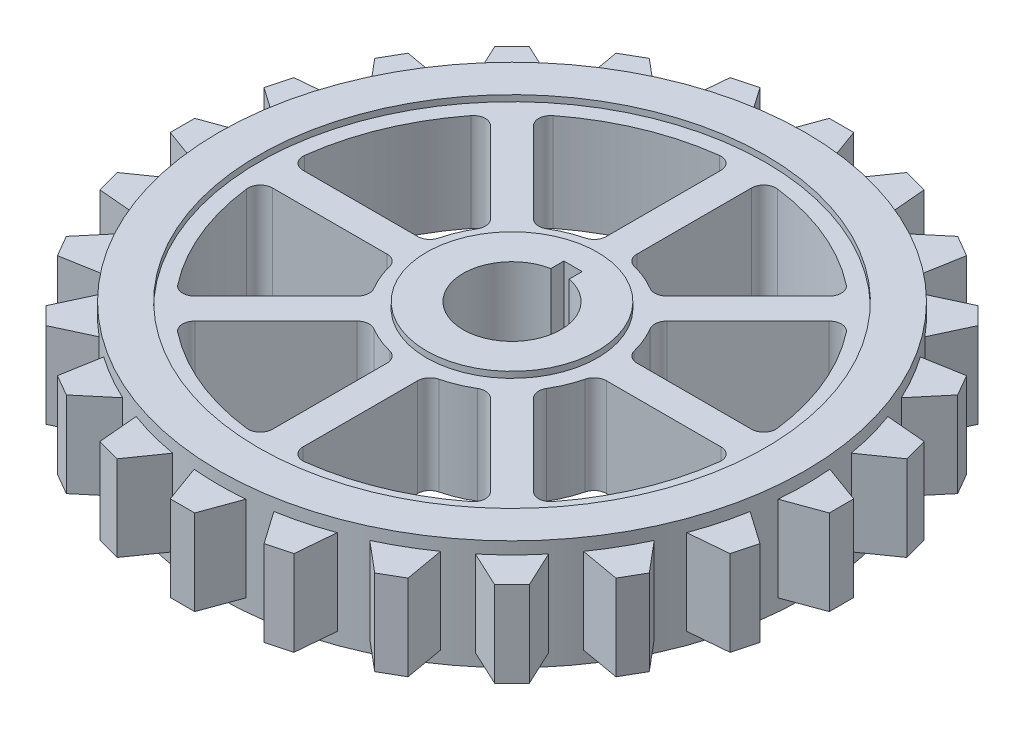
SolidWorks part; units mm, degrees
ref_plane "Front Plane" through (0, 0, 0) normal (0, 0, 1) x (1, 0, 0)
ref_plane "Top Plane" through (0, 0, 0) normal (0, 1, 0) x (1, 0, 0)
ref_plane "Right Plane" through (0, 0, 0) normal (1, 0, 0) x (0, 0, -1)
sketch "Sketch1" plane through (0, 0, 0) normal (0, 1, 0) x (1, 0, 0)
  line L0 (0, 0) -> (0, 10) construction
  line L1 (-1.5, 7.8581) -> (-1.5, 10)
  line L2 (-1.5, 10) -> (1.5, 10)
  line L6 (1.5, 7.8581) -> (1.5, 10)
  line L7 (0, 10) -> (0, 37.3528) construction
  line L8 (-2.5, 16.3095) -> (-2.5, 38.9198)
  line L9 (2.5, 16.3095) -> (2.5, 38.9198)
  line L10 (9.7648, 13.3003) -> (25.7527, 29.2882)
  line L11 (13.3003, 9.7648) -> (29.2882, 25.7527)
  line L12 (16.3095, 2.5) -> (38.9198, 2.5)
  line L13 (16.3095, -2.5) -> (38.9198, -2.5)
  line L14 (13.3003, -9.7648) -> (29.2882, -25.7527)
  line L15 (9.7648, -13.3003) -> (25.7527, -29.2882)
  line L16 (2.5, -16.3095) -> (2.5, -38.9198)
  line L17 (-2.5, -16.3095) -> (-2.5, -38.9198)
  line L18 (-9.7648, -13.3003) -> (-25.7527, -29.2882)
  line L19 (-13.3003, -9.7648) -> (-29.2882, -25.7527)
  line L20 (-16.3095, -2.5) -> (-38.9198, -2.5)
  line L21 (-16.3095, 2.5) -> (-38.9198, 2.5)
  line L22 (-13.3003, 9.7648) -> (-29.2882, 25.7527)
  line L23 (-9.7648, 13.3003) -> (-25.7527, 29.2882)
  line L24 (0, 48) -> (0, 65.9739) construction
  line L25 (-4.2386, 47.8125) -> (-2, 53.963)
  line L26 (-2, 53.963) -> (2, 53.963)
  line L27 (4.2386, 47.8125) -> (2, 53.963)
  line L28 (16.4689, 45.0863) -> (15.8985, 51.6066)
  line L29 (8.2806, 47.2803) -> (12.0348, 52.6418)
  line L30 (12.0348, 52.6418) -> (15.8985, 51.6066)
  line L31 (27.577, 39.2875) -> (28.7135, 45.7333)
  line L32 (20.2355, 43.5261) -> (25.2494, 47.7333)
  line L33 (25.2494, 47.7333) -> (28.7135, 45.7333)
  line L34 (36.8057, 30.8114) -> (39.5718, 36.7434)
  line L35 (30.8114, 36.8057) -> (36.7434, 39.5718)
  line L36 (36.7434, 39.5718) -> (39.5718, 36.7434)
  line L37 (43.5261, 20.2355) -> (47.7333, 25.2494)
  line L38 (39.2875, 27.577) -> (45.7333, 28.7135)
  line L39 (45.7333, 28.7135) -> (47.7333, 25.2494)
  line L40 (47.2803, 8.2806) -> (52.6418, 12.0348)
  line L41 (45.0863, 16.4689) -> (51.6066, 15.8985)
  line L42 (51.6066, 15.8985) -> (52.6418, 12.0348)
  line L43 (47.8125, -4.2386) -> (53.963, -2)
  line L44 (47.8125, 4.2386) -> (53.963, 2)
  line L45 (53.963, 2) -> (53.963, -2)
  line L46 (45.0863, -16.4689) -> (51.6066, -15.8985)
  line L47 (47.2803, -8.2806) -> (52.6418, -12.0348)
  line L48 (52.6418, -12.0348) -> (51.6066, -15.8985)
  line L49 (39.2875, -27.577) -> (45.7333, -28.7135)
  line L50 (43.5261, -20.2355) -> (47.7333, -25.2494)
  line L51 (47.7333, -25.2494) -> (45.7333, -28.7135)
  line L52 (30.8114, -36.8057) -> (36.7434, -39.5718)
  line L53 (36.8057, -30.8114) -> (39.5718, -36.7434)
  line L54 (39.5718, -36.7434) -> (36.7434, -39.5718)
  line L55 (20.2355, -43.5261) -> (25.2494, -47.7333)
  line L56 (27.577, -39.2875) -> (28.7135, -45.7333)
  line L57 (28.7135, -45.7333) -> (25.2494, -47.7333)
  line L58 (8.2806, -47.2803) -> (12.0348, -52.6418)
  line L59 (16.4689, -45.0863) -> (15.8985, -51.6066)
  line L60 (15.8985, -51.6066) -> (12.0348, -52.6418)
  line L61 (-4.2386, -47.8125) -> (-2, -53.963)
  line L62 (4.2386, -47.8125) -> (2, -53.963)
  line L63 (2, -53.963) -> (-2, -53.963)
  line L64 (-16.4689, -45.0863) -> (-15.8985, -51.6066)
  line L65 (-8.2806, -47.2803) -> (-12.0348, -52.6418)
  line L66 (-12.0348, -52.6418) -> (-15.8985, -51.6066)
  line L67 (-27.577, -39.2875) -> (-28.7135, -45.7333)
  line L68 (-20.2355, -43.5261) -> (-25.2494, -47.7333)
  line L69 (-25.2494, -47.7333) -> (-28.7135, -45.7333)
  line L70 (-36.8057, -30.8114) -> (-39.5718, -36.7434)
  line L71 (-30.8114, -36.8057) -> (-36.7434, -39.5718)
  line L72 (-36.7434, -39.5718) -> (-39.5718, -36.7434)
  line L73 (-43.5261, -20.2355) -> (-47.7333, -25.2494)
  line L74 (-39.2875, -27.577) -> (-45.7333, -28.7135)
  line L75 (-45.7333, -28.7135) -> (-47.7333, -25.2494)
  line L76 (-47.2803, -8.2806) -> (-52.6418, -12.0348)
  line L77 (-45.0863, -16.4689) -> (-51.6066, -15.8985)
  line L78 (-51.6066, -15.8985) -> (-52.6418, -12.0348)
  line L79 (-47.8125, 4.2386) -> (-53.963, 2)
  line L80 (-47.8125, -4.2386) -> (-53.963, -2)
  line L81 (-53.963, -2) -> (-53.963, 2)
  line L82 (-45.0863, 16.4689) -> (-51.6066, 15.8985)
  line L83 (-47.2803, 8.2806) -> (-52.6418, 12.0348)
  line L84 (-52.6418, 12.0348) -> (-51.6066, 15.8985)
  line L85 (-39.2875, 27.577) -> (-45.7333, 28.7135)
  line L86 (-43.5261, 20.2355) -> (-47.7333, 25.2494)
  line L87 (-47.7333, 25.2494) -> (-45.7333, 28.7135)
  line L88 (-30.8114, 36.8057) -> (-36.7434, 39.5718)
  line L89 (-36.8057, 30.8114) -> (-39.5718, 36.7434)
  line L90 (-39.5718, 36.7434) -> (-36.7434, 39.5718)
  line L91 (-20.2355, 43.5261) -> (-25.2494, 47.7333)
  line L92 (-27.577, 39.2875) -> (-28.7135, 45.7333)
  line L93 (-28.7135, 45.7333) -> (-25.2494, 47.7333)
  line L94 (-8.2806, 47.2803) -> (-12.0348, 52.6418)
  line L95 (-16.4689, 45.0863) -> (-15.8985, 51.6066)
  line L96 (-15.8985, 51.6066) -> (-12.0348, 52.6418)
  line L97 (-8.2806, 47.2803) -> (-16.4689, 45.0863) construction
  arc A0 (-16.4689, 45.0863) -> (-20.2355, 43.5261) centre (0, 0) ccw
  circle A1 centre (0, 0) radius 41.5
  arc A2 (-29.2882, 25.7527) -> (-38.9198, 2.5) centre (0, 0) ccw
  circle A4 centre (0, 0) radius 14
  arc A5 (-1.5, 7.8581) -> (1.5, 7.8581) centre (0, 0) ccw
  arc A6 (-13.3003, 9.7648) -> (-16.3095, 2.5) centre (0, 0) ccw
  arc A7 (-2.5, 38.9198) -> (-25.7527, 29.2882) centre (0, 0) ccw
  arc A8 (25.7527, 29.2882) -> (2.5, 38.9198) centre (0, 0) ccw
  arc A9 (38.9198, 2.5) -> (29.2882, 25.7527) centre (0, 0) ccw
  arc A10 (29.2882, -25.7527) -> (38.9198, -2.5) centre (0, 0) ccw
  arc A11 (2.5, -38.9198) -> (25.7527, -29.2882) centre (0, 0) ccw
  arc A12 (-25.7527, -29.2882) -> (-2.5, -38.9198) centre (0, 0) ccw
  arc A13 (-38.9198, -2.5) -> (-29.2882, -25.7527) centre (0, 0) ccw
  arc A14 (-2.5, 16.3095) -> (-9.7648, 13.3003) centre (0, 0) ccw
  arc A15 (9.7648, 13.3003) -> (2.5, 16.3095) centre (0, 0) ccw
  arc A16 (16.3095, 2.5) -> (13.3003, 9.7648) centre (0, 0) ccw
  arc A17 (13.3003, -9.7648) -> (16.3095, -2.5) centre (0, 0) ccw
  arc A18 (2.5, -16.3095) -> (9.7648, -13.3003) centre (0, 0) ccw
  arc A19 (-9.7648, -13.3003) -> (-2.5, -16.3095) centre (0, 0) ccw
  arc A20 (-16.3095, -2.5) -> (-13.3003, -9.7648) centre (0, 0) ccw
  circle A21 centre (0, 0) radius 14
  circle A22 centre (0, 0) radius 14
  circle A23 centre (0, 0) radius 14
  circle A24 centre (0, 0) radius 14
  circle A25 centre (0, 0) radius 14
  circle A26 centre (0, 0) radius 14
  circle A27 centre (0, 0) radius 14
  circle A28 centre (0, 0) radius 14
  circle A29 centre (0, 0) radius 14
  circle A30 centre (0, 0) radius 14
  circle A31 centre (0, 0) radius 14
  circle A32 centre (0, 0) radius 14
  circle A33 centre (0, 0) radius 14
  circle A34 centre (0, 0) radius 14
  circle A35 centre (0, 0) radius 14
  circle A36 centre (0, 0) radius 14
  circle A37 centre (0, 0) radius 14
  circle A38 centre (0, 0) radius 14
  circle A39 centre (0, 0) radius 14
  circle A40 centre (0, 0) radius 14
  circle A41 centre (0, 0) radius 14
  circle A42 centre (0, 0) radius 14
  circle A43 centre (0, 0) radius 14
  arc A44 (-4.2386, 47.8125) -> (-8.2806, 47.2803) centre (0, 0) ccw
  arc A45 (8.2806, 47.2803) -> (4.2386, 47.8125) centre (0, 0) ccw
  arc A46 (20.2355, 43.5261) -> (16.4689, 45.0863) centre (0, 0) ccw
  arc A47 (30.8114, 36.8057) -> (27.577, 39.2875) centre (0, 0) ccw
  arc A48 (39.2875, 27.577) -> (36.8057, 30.8114) centre (0, 0) ccw
  arc A49 (45.0863, 16.4689) -> (43.5261, 20.2355) centre (0, 0) ccw
  arc A50 (47.8125, 4.2386) -> (47.2803, 8.2806) centre (0, 0) ccw
  arc A51 (47.2803, -8.2806) -> (47.8125, -4.2386) centre (0, 0) ccw
  arc A52 (43.5261, -20.2355) -> (45.0863, -16.4689) centre (0, 0) ccw
  arc A53 (36.8057, -30.8114) -> (39.2875, -27.577) centre (0, 0) ccw
  arc A54 (27.577, -39.2875) -> (30.8114, -36.8057) centre (0, 0) ccw
  arc A55 (16.4689, -45.0863) -> (20.2355, -43.5261) centre (0, 0) ccw
  arc A56 (4.2386, -47.8125) -> (8.2806, -47.2803) centre (0, 0) ccw
  arc A57 (-8.2806, -47.2803) -> (-4.2386, -47.8125) centre (0, 0) ccw
  arc A58 (-20.2355, -43.5261) -> (-16.4689, -45.0863) centre (0, 0) ccw
  arc A59 (-30.8114, -36.8057) -> (-27.577, -39.2875) centre (0, 0) ccw
  arc A60 (-39.2875, -27.577) -> (-36.8057, -30.8114) centre (0, 0) ccw
  arc A61 (-45.0863, -16.4689) -> (-43.5261, -20.2355) centre (0, 0) ccw
  arc A62 (-47.8125, -4.2386) -> (-47.2803, -8.2806) centre (0, 0) ccw
  arc A63 (-47.2803, 8.2806) -> (-47.8125, 4.2386) centre (0, 0) ccw
  arc A64 (-43.5261, 20.2355) -> (-45.0863, 16.4689) centre (0, 0) ccw
  arc A65 (-36.8057, 30.8114) -> (-39.2875, 27.577) centre (0, 0) ccw
  arc A66 (-27.577, 39.2875) -> (-30.8114, 36.8057) centre (0, 0) ccw
  circle A67 centre (0, 0) radius 48
  circle A68 centre (0, 0) radius 54 construction
  point P48 (0, 0)
  point P50 (0, 53.963)
  point P169 (0, 0)
  dimension "D1" = 96
  dimension "D2" = 6.5
  dimension "D3" = 2.5
  dimension "D4" = 6
  dimension "D5" = 28
  dimension "D6" = 16
  dimension "D9" = 2.5
  dimension "D7" = 1.5
  dimension "D8" = 10
  dimension "D10" = 5
  dimension "D12" = 2
  dimension "D13" = 40
  dimension "D14" = 24
  dimension "D11" = 8
extrude "Boss-Extrude1" add sketch "Sketch1" along normal mid plane 14 contours A67 L88 L90 L89 | A67 L85 L87 L86 | A67 L82 L84 L83 | A67 L79 L81 L80 | A67 L76 L78 L77 | A67 L73 L75 L74 | A67 L70 L72 L71 | A67 L67 L69 L68 | A67 L64 L66 L65 | A67 L61 L63 L62 | A67 L58 L60 L59 | A67 L55 L57 L56 | A67 L52 L54 L53 | A67 L49 L51 L50 | A67 L46 L48 L47 | A67 L43 L45 L44 | A67 L40 L42 L41 | A67 L37 L39 L38 | A67 L34 L36 L35 | A67 L31 L33 L32 | A67 L28 L30 L29 | A67 L27 L26 L25 | A67 L94 L96 L95 | A67 L91 L93 L92 | A56 A67 A55 A54 A53 A52 A51 A50 A49 A48 A47 A46 A45 A44 A0 A66 A65 A64 A63 A62 A61 A60 A59 A58 A57 A1 | A1 A4 L22 A6 L21 A2 L8 A14 L23 A7 L10 A15 L9 A8 L12 A16 L11 A9 L14 A17 L13 A10 L16 A18 L15 A11 L18 A19 L17 A12 L20 A20 L19 A13 | A4 A5 L1 L2 L6 region at (0, 0, -46.6424) region at (0, 0, -50.5947) region at (-13.0949, 0, -48.8707) region at (13.0949, 0, -48.8707) region at (-25.2973, 0, -43.8163) region at (25.2973, 0, -43.8163) region at (-35.7758, 0, -35.7758) region at (35.7758, 0, -35.7758) region at (-43.8163, 0, -25.2973) region at (43.8163, 0, -25.2973) region at (-48.8707, 0, -13.0949) region at (48.8707, 0, -13.0949) region at (-50.5947, 0, 0) region at (50.5947, 0, 0) region at (-48.8707, 0, 13.0949) region at (-43.8163, 0, 25.2973) region at (48.8707, 0, 13.0949) region at (-35.7758, 0, 35.7758) region at (43.8163, 0, 25.2973) region at (-25.2973, 0, 43.8163) region at (35.7758, 0, 35.7758) region at (-13.0949, 0, 48.8707) region at (25.2973, 0, 43.8163) region at (0, 0, 50.5947) region at (13.0949, 0, 48.8707) region at (-40.3262, 0, 0) region at (-13.604, 0, 0)
extrude "Boss-Extrude2" add sketch "Sketch1<4>" along normal mid plane 18 contours A56 A67 A55 A54 A53 A52 A51 A50 A49 A48 A47 A46 A45 A44 A0 A66 A65 A64 A63 A62 A61 A60 A59 A58 A57 A1 | A4 A5 L1 L2 L6 region at (0, 0, -46.6424) region at (-13.604, 0, 0)
sketch "Sketch1<4>" plane through (0, 0, 0) normal (0, 1, 0) x (1, 0, 0) same geometry as "Sketch1"
extrude "Boss-Extrude3" add sketch "Sketch1<5>" along normal mid plane 16 contours A1 A4 L22 A6 L21 A2 L8 A14 L23 A7 L10 A15 L9 A8 L12 A16 L11 A9 L14 A17 L13 A10 L16 A18 L15 A11 L18 A19 L17 A12 L20 A20 L19 A13 region at (-40.3262, 0, 0)
sketch "Sketch1<5>" plane through (0, 0, 0) normal (0, 1, 0) x (1, 0, 0) same geometry as "Sketch1"
fillet "Fillet2" radius 2 32 edges at (-38.9198, 0, 2.5) (-29.2882, 0, 25.7527) (-13.3003, 0, 9.7648) (-16.3095, 0, 2.5) (-25.7527, 0, 29.2882) (-2.5, 0, 38.9198) (-2.5, 0, 16.3095) (-9.7648, 0, 13.3003) (2.5, 0, 38.9198) (25.7527, 0, 29.2882) (9.7648, 0, 13.3003) (2.5, 0, 16.3095) (29.2882, 0, 25.7527) (38.9198, 0, 2.5) (16.3095, 0, 2.5) (13.3003, 0, 9.7648) (38.9198, 0, -2.5) (29.2882, 0, -25.7527) (13.3003, 0, -9.7648) (16.3095, 0, -2.5) (25.7527, 0, -29.2882) (2.5, 0, -38.9198) (2.5, 0, -16.3095) (9.7648, 0, -13.3003) (-9.7648, 0, -13.3003) (-2.5, 0, -16.3095) (-29.2882, 0, -25.7527) (-38.9198, 0, -2.5) (-16.3095, 0, -2.5) (-13.3003, 0, -9.7648) (-25.7527, 0, -29.2882) (-2.5, 0, -38.9198)
